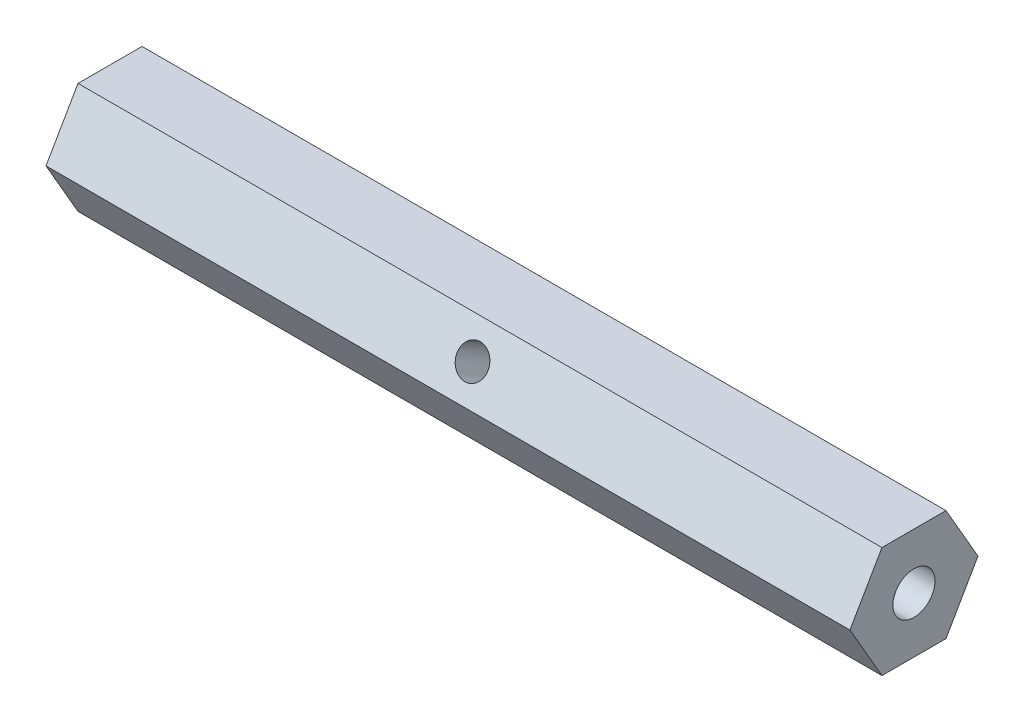
SolidWorks part; units mm, degrees
material "6061 Alloy"
ref_plane "Front" through (0, 0, 0) normal (0, 0, 1) x (1, 0, 0)
ref_plane "Top" through (0, 0, 0) normal (0, 1, 0) x (1, 0, 0)
ref_plane "Right" through (0, 0, 0) normal (1, 0, 0) x (0, 0, -1)
sketch "Sketch1" plane through (0, 0, 0) normal (1, 0, 0) x (0, 0, -1)
  line L1 (3.6662, 6.35) -> (-3.6662, 6.35)
  line L2 (-3.6662, 6.35) -> (-7.3323, 0)
  line L3 (-7.3323, 0) -> (-3.6662, -6.35)
  line L4 (-3.6662, -6.35) -> (3.6662, -6.35)
  line L5 (3.6662, -6.35) -> (7.3323, 0)
  line L6 (7.3323, 0) -> (3.6662, 6.35)
  circle A0 centre (0, 0) radius 6.35 construction
  dimension "D1" = 12.7
extrude "Boss-Extrude1" add sketch "Sketch1" along normal blind 92.075
sketch "Sketch2" plane through (92.075, 0, 0) normal (1, 0, 0) x (0, 0, -1)
  circle A0 centre (0, 0) radius 2.413
  dimension "D1" = 4.826
extrude "Cut-Extrude1" cut sketch "Sketch2" against normal blind 25.4
sketch "Sketch3" plane through (0, 3.175, 5.4993) normal (0, 0.5, 0.866) x (1, 0, 0)
  line L0 (0, 3.6662) -> (0, -3.6662) construction
  line L1 (0, 0) -> (47.0154, 0) construction
  circle A0 centre (47.0154, 0) radius 1.778
  point P7 (0, 0)
  dimension "D2" = 3.556
  dimension "D1" = 47.0154
extrude "Cut-Extrude2" cut sketch "Sketch3" against normal blind 25.4
